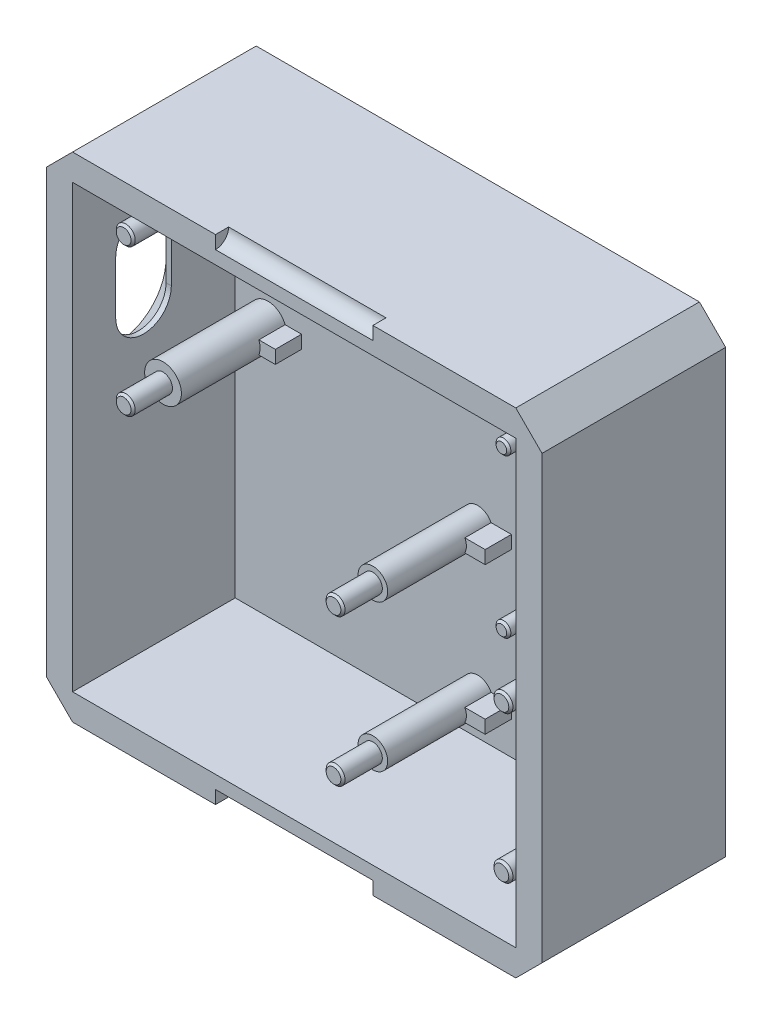
SolidWorks part; units mm, degrees
ref_plane "Front Plane" through (0, 0, 0) normal (0, 0, 1) x (1, 0, 0)
ref_plane "Top Plane" through (0, 0, 0) normal (0, 1, 0) x (1, 0, 0)
ref_plane "Right Plane" through (0, 0, 0) normal (1, 0, 0) x (0, 0, -1)
sketch "Sketch1" plane through (0, 0, 0) normal (0, 0, 1) x (1, 0, 0)
  line L0 (0, 0) -> (-22.86, 0) construction
  line L2 (-22.86, 8.89) -> (-22.86, -8.89) construction
  line L4 (22.86, 9.555) -> (22.86, -9.555) construction
  line L7 (0, 0) -> (22.86, 0) construction
  circle A0 centre (-22.86, 8.89) radius 1.5875 construction
  circle A1 centre (22.86, 9.555) radius 1.5875 construction
  circle A2 centre (22.86, -9.555) radius 1.5875 construction
  circle A3 centre (-22.86, -8.89) radius 1.5875 construction
  circle A4 centre (-22.86, 8.89) radius 2.2225
  circle A5 centre (-22.86, -8.89) radius 2.2225
  circle A6 centre (22.86, 9.555) radius 1.5
  circle A7 centre (22.86, -9.555) radius 1.5
  point P0 (0, 0)
  dimension "D1" = 0.635
  dimension "D2" = 3.175
  dimension "D3" = 3
  dimension "D7" = 0.0875
  dimension "D4" = 45.72
  dimension "D5" = 17.78
  dimension "D6" = 19.11
extrude "Boss-Extrude1" add sketch "Sketch1" against normal blind 12.7
sketch "Sketch2" plane through (0, 0, -12.7) normal (0, 0, -1) x (-1, 0, 0)
  line L0 (0, 13.6525) -> (0, 0) construction
  line L1 (-26.8224, 13.6525) -> (26.8224, 13.6525)
  line L2 (-26.8224, 13.6525) -> (-26.8224, -39.751)
  line L3 (-26.8224, -39.751) -> (26.8224, -39.751)
  line L4 (26.8224, 13.6525) -> (26.8224, -39.751)
  line L5 (-26.8224, 13.6525) -> (26.8224, -39.751) construction
  line L6 (-26.8224, -39.751) -> (26.8224, 13.6525) construction
  circle A0 centre (22.86, 8.89) radius 2.2225 construction
  point P0 (0, -13.0492)
  dimension "D1" = 4.7625
  dimension "D2" = 53.6448
  dimension "D3" = 53.4035
extrude "Boss-Extrude2" add sketch "Sketch2" along normal blind 2.54
sketch "Sketch3" plane through (0, 0, -15.24) normal (0, 0, 1) x (1, 0, 0)
  line L1 (-26.8224, 13.6525) -> (26.8224, 13.6525)
  line L2 (-26.8224, 13.6525) -> (-26.8224, 16.8275)
  line L3 (-26.8224, 16.8275) -> (26.8224, 16.8275)
  line L4 (26.8224, 13.6525) -> (26.8224, 16.8275)
  line L5 (-26.8224, -39.751) -> (26.8224, -39.751)
  line L6 (-26.8224, -39.751) -> (-26.8224, -42.926)
  line L7 (-26.8224, -42.926) -> (26.8224, -42.926)
  line L8 (26.8224, -39.751) -> (26.8224, -42.926)
  dimension "D1" = 3.175
  dimension "D2" = 3.175
extrude "Boss-Extrude3" add sketch "Sketch3" along normal blind 22.225
sketch "Sketch4" plane through (0, 0, 0) normal (0, 0, 1) x (1, 0, 0)
  circle A0 centre (-22.86, 8.89) radius 1.143
  circle A1 centre (22.86, 9.555) radius 0.889
  circle A2 centre (-22.86, -8.89) radius 1.143
  circle A3 centre (22.86, -9.555) radius 0.889
  dimension "D1" = 2.286
  dimension "D2" = 1.778
extrude "Boss-Extrude4" add sketch "Sketch4" along normal blind 4.7625
sketch "Sketch5" plane through (0, 0, -12.7) normal (0, 0, 1) x (1, 0, 0)
  line L0 (22.86, 9.555) -> (22.86, -9.555) construction
  line L1 (2.54, -17.175) -> (22.86, -17.175) construction
  line L2 (2.54, -17.175) -> (2.54, -34.955) construction
  line L3 (2.54, -34.955) -> (22.86, -34.955) construction
  line L4 (22.86, -17.175) -> (22.86, -34.955) construction
  circle A0 centre (22.86, -17.175) radius 1.7907
  circle A1 centre (2.54, -17.175) radius 1.7907
  circle A2 centre (2.54, -34.955) radius 1.7907
  circle A3 centre (22.86, -34.955) radius 1.7907
  circle A4 centre (22.86, -9.555) radius 1.5 construction
  dimension "D3" = 7.62
  dimension "D4" = 3.5814
  dimension "D1" = 17.78
  dimension "D2" = 20.32
extrude "Boss-Extrude5" add sketch "Sketch5" along normal up to surface (12.7 mm away) up to face at (23.749, -9.555, 0)
sketch "Sketch6" plane through (0, 0, 0) normal (0, 0, 1) x (1, 0, 0)
  circle A0 centre (2.54, -17.175) radius 1.143
  circle A1 centre (22.86, -17.175) radius 1.143
  circle A2 centre (2.54, -34.955) radius 1.143
  circle A3 centre (22.86, -34.955) radius 1.143
  dimension "D1" = 2.286
extrude "Boss-Extrude6" add sketch "Sketch6" along normal up to surface (4.7625 mm away) up to face at (23.749, -9.555, 4.7625)
sketch "Sketch7" plane through (26.8224, 0, 0) normal (1, 0, 0) x (0, 0, -1)
  line L1 (-6.985, 16.8275) -> (15.24, 16.8275)
  line L2 (-6.985, 16.8275) -> (-6.985, -42.926)
  line L3 (-6.985, -42.926) -> (15.24, -42.926)
  line L4 (15.24, 16.8275) -> (15.24, -42.926)
extrude "Boss-Extrude7" add sketch "Sketch7" along normal blind 3.175
sketch "Sketch8" plane through (-26.8224, 0, 0) normal (-1, 0, 0) x (0, 0, 1)
  line L0 (6.985, 16.8275) -> (6.985, -42.926)
  line L1 (6.985, 13.6525) -> (6.985, -39.751) construction
  line L6 (6.985, -42.926) -> (-15.24, -42.926)
  line L7 (-15.24, -42.926) -> (-15.24, 16.8275)
  line L8 (-15.24, 16.8275) -> (6.985, 16.8275)
  line L9 (-1.6002, 3.175) -> (-1.6002, -3.175) construction
  line L10 (1.7653, 3.175) -> (1.7653, -3.175)
  line L11 (-4.9657, 3.175) -> (-4.9657, -3.175)
  line L12 (0, 0) -> (-1.6002, 0) construction
  arc A0 (1.7653, 3.175) -> (-4.9657, 3.175) centre (-1.6002, 3.175) ccw
  arc A1 (-4.9657, -3.175) -> (1.7653, -3.175) centre (-1.6002, -3.175) ccw
  point P5 (-1.6002, 0)
  dimension "D2" = 6.731
  dimension "D1" = 13.6398
  dimension "D3" = 6.35
extrude "Boss-Extrude8" add sketch "Sketch8" along normal blind 3.175
sketch "Sketch9" plane through (0, 0, 0) normal (1, 0, 0) x (0, 0, -1)
  line L1 (15.24, 16.8275) -> (-6.985, 16.8275) construction
  line L6 (15.24, -8.5725) -> (15.24, 2.2561)
  line L7 (-6.985, -42.926) -> (15.24, -42.926) construction
  line L8 (15.24, -42.926) -> (15.24, 16.8275) construction
  line L9 (15.24, 2.2561) -> (17.6902, 7.3195)
  line L10 (17.6902, 7.3195) -> (27.3372, -2.5321)
  line L11 (27.3372, -2.5321) -> (17.526, -35.2226)
  line L12 (17.526, -35.2226) -> (17.526, -21.9684)
  line L13 (17.526, -21.9684) -> (23.0415, -3.591)
  line L14 (23.0415, -3.591) -> (19.4335, 0.0935)
  line L15 (19.4335, 0.0935) -> (15.24, -8.5725)
  line L16 (19.1185, -0.5575) -> (14.8727, 1.497) construction
  line L17 (20.6175, -1.1155) -> (23.3396, 1.5502) construction
  line L18 (21.5888, -8.4313) -> (25.238, -9.5265) construction
  dimension "D1" = 2.286
  dimension "D2" = 3.81
  dimension "D3" = 2.4502
  dimension "D4" = 12.0972
  dimension "D5" = 9.508
  dimension "D6" = 19.3596
  dimension "D7" = 7.7034
  dimension "D8" = 14.5714
  dimension "D9" = 25.4
  dimension "D10" = 3.4647
  dimension "D11" = 0.7233
  dimension "D12" = 4.8404
extrude "Boss-Extrude9" add sketch "Sketch9" along normal mid plane 12.7
fillet "Fillet1" radius 0.508 8 edges at (0, -21.9684, -17.526) (0, -35.2226, -17.526) (0, -2.5321, -27.3372) (0, -3.591, -23.0415) (0, 0.0935, -19.4335) (0, -8.5725, -15.24) (0, 2.2561, -15.24) (0, 7.3195, -17.6902)
fillet "Fillet2" radius 0.0254 32 edges at (6.35, 6.9492, -17.7507) (-6.35, 6.9492, -17.7507) (-6.35, 5.46, -16.7904) (-6.35, -2.1084, -15.24) (-6.35, 3.977, -15.6345) (6.35, -8.5754, -15.2528) (-6.35, -8.5754, -15.2528) (-6.35, -4.5123, -17.2048) (-6.35, -0.2768, -19.4941) (-6.35, -1.8997, -21.3854) (-6.35, 2.2427, -22.6615) (-6.35, -2.5517, -27.2577) (-6.35, -3.6106, -22.962) (-6.35, -12.8876, -20.2514) (-6.35, -21.9692, -17.5314) (-6.35, -17.3641, -22.8858) (-6.35, -26.9029, -17.526) (-6.35, -32.2654, -17.9602) (6.35, -21.9692, -17.5314) (6.35, -32.2654, -17.9602) (6.35, -26.9029, -17.526) (6.35, -3.6106, -22.962) (6.35, -2.5517, -27.2577) (6.35, -17.3641, -22.8858) (6.35, -12.8876, -20.2514) (6.35, -1.8997, -21.3854) (6.35, -0.2768, -19.4941) (6.35, -4.5123, -17.2048) (6.35, 2.2427, -22.6615) (6.35, 3.977, -15.6345) (6.35, 5.46, -16.7904) (6.35, -2.1084, -15.24)
chamfer "Chamfer1" distance 3.175 angle 45 4 edges at (-29.9974, -42.926, -4.1275) (29.9974, -42.926, -4.1275) (29.9974, 16.8275, -4.1275) (-29.9974, 16.8275, -4.1275)
chamfer "Chamfer2" distance 2.54 angle 45 4 edges at (-29.9974, 0, 1.7653) (-29.9974, -6.5405, -1.6002) (-29.9974, 0, -4.9657) (-29.9974, 6.5405, -1.6002)
sketch "Sketch10" plane through (0, 0, 0) normal (1, 0, 0) x (0, 0, -1)
  circle A0 centre (-6.985, 16.8275) radius 1.5875
  circle A1 centre (-6.985, -42.926) radius 1.5875
  dimension "D1" = 3.175
  dimension "D2" = 3.175
extrude "Cut-Extrude1" cut sketch "Sketch10" against normal blind 9.525 and the other way blind 9.525
chamfer "Chamfer3" distance 0.254 angle 45 8 edges at (24.003, -34.955, 4.7625) (3.683, -34.955, 4.7625) (3.683, -17.175, 4.7625) (24.003, -17.175, 4.7625) (23.749, -9.555, 4.7625) (23.749, 9.555, 4.7625) (-21.717, -8.89, 4.7625) (-21.717, 8.89, 4.7625)
sketch "Sketch12" plane through (0, 0, -12.7) normal (0, 0, 1) x (1, 0, 0)
  line L0 (2.54, -34.955) -> (3.429, -34.955) construction
  line L1 (-21.971, 9.6837) -> (-18.796, 9.6837)
  line L2 (-21.971, 9.6837) -> (-21.971, 8.0962)
  line L3 (-21.971, 8.0962) -> (-18.796, 8.0962)
  line L4 (-18.796, 9.6837) -> (-18.796, 8.0962)
  line L5 (-21.971, -8.0963) -> (-18.796, -8.0963)
  line L6 (-21.971, -8.0963) -> (-21.971, -9.6838)
  line L7 (-21.971, -9.6838) -> (-18.796, -9.6838)
  line L8 (-18.796, -8.0963) -> (-18.796, -9.6838)
  line L9 (3.429, -16.3813) -> (6.604, -16.3813)
  line L10 (3.429, -16.3813) -> (3.429, -17.9688)
  line L11 (3.429, -17.9688) -> (6.604, -17.9688)
  line L12 (6.604, -16.3813) -> (6.604, -17.9688)
  line L13 (21.971, -16.3813) -> (18.796, -16.3813)
  line L14 (21.971, -16.3813) -> (21.971, -17.9688)
  line L15 (21.971, -17.9688) -> (18.796, -17.9688)
  line L16 (18.796, -16.3813) -> (18.796, -17.9688)
  line L17 (3.429, -34.1613) -> (6.604, -34.1613)
  line L18 (3.429, -34.1613) -> (3.429, -35.7487)
  line L19 (3.429, -35.7487) -> (6.604, -35.7487)
  line L20 (6.604, -34.1613) -> (6.604, -35.7487)
  line L21 (21.971, -34.1613) -> (18.796, -34.1613)
  line L22 (21.971, -34.1613) -> (21.971, -35.7487)
  line L23 (21.971, -35.7487) -> (18.796, -35.7487)
  line L24 (18.796, -34.1613) -> (18.796, -35.7487)
  line L25 (3.429, -34.955) -> (18.796, -34.955) construction
  line L26 (2.54, -17.175) -> (3.429, -17.175) construction
  line L27 (3.429, -17.175) -> (18.796, -17.175) construction
  line L28 (-22.86, 8.89) -> (-21.971, 8.89) construction
  line L29 (-22.86, -8.89) -> (-21.971, -8.89) construction
  line L30 (22.86, 9.555) -> (21.971, 9.555) construction
  line L31 (21.971, 10.3487) -> (18.796, 10.3487)
  line L32 (21.971, 10.3487) -> (21.971, 8.7613)
  line L33 (21.971, 8.7613) -> (18.796, 8.7613)
  line L34 (18.796, 10.3487) -> (18.796, 8.7613)
  line L35 (21.971, -8.7613) -> (18.796, -8.7613)
  line L36 (21.971, -8.7613) -> (21.971, -10.3487)
  line L37 (21.971, -10.3487) -> (18.796, -10.3487)
  line L38 (18.796, -8.7613) -> (18.796, -10.3487)
  line L39 (22.86, -9.555) -> (21.971, -9.555) construction
  circle A1 centre (22.86, -34.955) radius 0.889 construction
  circle A2 centre (2.54, -34.955) radius 0.889 construction
  circle A3 centre (2.54, -17.175) radius 0.889 construction
  circle A4 centre (22.86, -17.175) radius 0.889 construction
  circle A5 centre (-22.86, 8.89) radius 0.889 construction
  circle A6 centre (-22.86, -8.89) radius 0.889 construction
  circle A7 centre (22.86, 9.555) radius 0.635 construction
  circle A8 centre (22.86, -9.555) radius 0.635 construction
  point P50 (21.7105, -9.555)
  point P61 (21.971, -16.4002)
  dimension "D3" = 4.064
  dimension "D4" = 4.064
  dimension "D5" = 4.064
  dimension "D7" = 4.064
  dimension "D8" = 4.064
  dimension "D1" = 3.175
  dimension "D2" = 1.5875
  dimension "D6" = 4.064
  dimension "D9" = 4.064
  dimension "D10" = 4.064
extrude "Boss-Extrude10" add sketch "Sketch12" along normal blind 3.175
